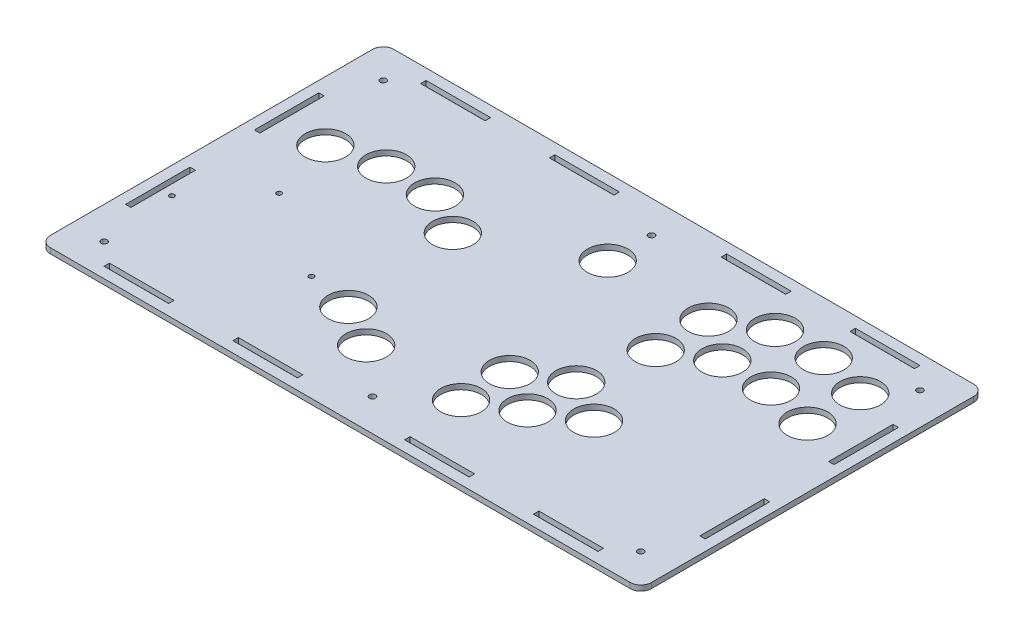
SolidWorks part; units mm, degrees
ref_plane "Front Plane" through (0, 0, 0) normal (0, 0, 1) x (1, 0, 0)
ref_plane "Top Plane" through (0, 0, 0) normal (0, 1, 0) x (1, 0, 0)
ref_plane "Right Plane" through (0, 0, 0) normal (1, 0, 0) x (0, 0, -1)
ref_axis "Axis1" through (0, 0, -135.9953) along (0, 0, 1)
sketch "Panel Profile" plane through (0, 0, 0) normal (0, 1, 0) x (1, 0, 0)
  line L1 (-177.8, 101.6) -> (177.8, 101.6)
  line L2 (-177.8, 101.6) -> (-177.8, -101.6)
  line L3 (-177.8, -101.6) -> (177.8, -101.6)
  line L4 (177.8, 101.6) -> (177.8, -101.6)
  line L5 (-177.8, 101.6) -> (177.8, -101.6) construction
  line L6 (-177.8, -101.6) -> (177.8, 101.6) construction
  point P0 (0, 0)
  dimension "D1" = 203.2
  dimension "D2" = 355.6
sketch "Right Hand Buttons" plane through (0, 0, 0) normal (0, 1, 0) x (1, 0, 0)
  line L0 (85, 70.6) -> (113.8, 70.6) construction
  line L5 (-55, 0) -> (55, 0) construction
  line L6 (0, -55) -> (0, 55) construction
  line L7 (60, 56.2) -> (60, 25) construction
  line L8 (85, 70.6) -> (85, 39.4) construction
  line L9 (113.8, 70.6) -> (113.8, 39.4) construction
  line L10 (142.6, 63.4) -> (142.6, 32.2) construction
  circle A0 centre (60, 56.2) radius 12
  circle A1 centre (85, 70.6) radius 12
  circle A2 centre (113.8, 70.6) radius 12
  circle A7 centre (142.6, 63.4) radius 12
  circle A8 centre (60, 25) radius 12
  circle A9 centre (85, 39.4) radius 12
  circle A10 centre (113.8, 39.4) radius 12
  circle A11 centre (142.6, 32.2) radius 12
  point P0 (0, 0)
  dimension "D2" = 24
  dimension "D1" = 25
  dimension "D3" = 28.8
  dimension "D4" = 14.4
  dimension "D5" = 25
  dimension "D6" = 28.8
  dimension "D7" = 7.2
  dimension "D8" = 31.2
  dimension "D9" = 60
extrude "Panel-Profile" add sketch "Panel Profile" against normal blind 3.175
extrude "Right Buttons" cut sketch "Right Hand Buttons" against normal blind 3.175 and the other way through all
sketch "Sketch4" plane through (0, 0, 0) normal (0, 1, 0) x (1, 0, 0)
  line L0 (28.0585, -29.4) -> (28.0585, -58.2) construction
  line L1 (53, -15) -> (53, -43.8) construction
  line L2 (28.0585, -29.4) -> (53, -15) construction
  line L3 (28.0585, -29.4) -> (53, -43.8) construction
  line L4 (53, -15) -> (77.9415, -29.4) construction
  line L5 (53, -43.8) -> (77.9415, -29.4) construction
  line L6 (28.0585, -58.2) -> (53, -43.8) construction
  circle A0 centre (53, -43.8) radius 12
  circle A1 centre (53, -15) radius 12
  circle A2 centre (77.9415, -29.4) radius 12
  circle A3 centre (28.0585, -29.4) radius 12
  circle A4 centre (28.0585, -58.2) radius 12
  circle A5 centre (60, 25) radius 12 construction
  dimension "D1" = 24
  dimension "D3" = 40
  dimension "D4" = 7
  dimension "D2" = 28.8
extrude "C-Stick" cut sketch "Sketch4" against normal blind 3.175
sketch "Start Button" plane through (0, 0, 0) normal (0, 1, 0) x (1, 0, 0)
  line L0 (0, -55) -> (0, 55) construction
  line L1 (177.8, 101.6) -> (-177.8, 101.6) construction
  circle A0 centre (0, 56.6) radius 12
  dimension "D1" = 24
  dimension "D2" = 45
extrude "Start" cut sketch "Start Button" against normal blind 3.175 contours A0
sketch "Sketch7" plane through (0, 0, 0) normal (0, 1, 0) x (1, 0, 0)
  line L0 (0, -55) -> (0, 55) construction
  circle A0 centre (142.6, 32.2) radius 12 construction
  circle A1 centre (113.8, 39.4) radius 12 construction
  circle A2 centre (85, 39.4) radius 12 construction
  circle A3 centre (60, 25) radius 12 construction
  circle A4 centre (142.6, 32.2) radius 12 construction
  circle A5 centre (113.8, 39.4) radius 12 construction
  circle A6 centre (85, 39.4) radius 12 construction
  circle A7 centre (60, 25) radius 12 construction
  circle A8 centre (-142.6, 32.2) radius 12
  circle A9 centre (-113.8, 39.4) radius 12
  circle A10 centre (-85, 39.4) radius 12
  circle A11 centre (-60, 25) radius 12
  circle A12 centre (28.0585, -58.2) radius 12 construction
  circle A13 centre (53, -43.8) radius 12 construction
  circle A14 centre (28.0585, -58.2) radius 12 construction
  circle A15 centre (53, -43.8) radius 12 construction
  circle A16 centre (-53, -43.8) radius 12
  circle A17 centre (-28.0585, -58.2) radius 12
extrude "L-Stick" cut sketch "Sketch7" against normal blind 3.175
sketch "Sketch8" plane through (0, 0, 0) normal (0, 1, 0) x (1, 0, 0)
  line L0 (0, 135.9953) -> (0, -135.9953) construction
  line L1 (177.8, 101.6) -> (-177.8, 101.6) construction
  line L2 (-177.8, 101.6) -> (-177.8, -101.6) construction
  line L3 (-177.8, -101.6) -> (177.8, -101.6) construction
  line L4 (177.8, -101.6) -> (177.8, 101.6) construction
  circle A0 centre (-158.75, 82.55) radius 1.8288
  circle A1 centre (0, 82.55) radius 1.8288
  circle A2 centre (158.75, 82.55) radius 1.8288
  circle A3 centre (-158.75, -82.55) radius 1.8288
  circle A4 centre (0, -82.55) radius 1.8288
  circle A5 centre (158.75, -82.55) radius 1.8288
  dimension "D1" = 3.6576
  dimension "D2" = 19.05
  dimension "D3" = 19.05
  dimension "D4" = 19.05
  dimension "D5" = 19.05
extrude "Cut-Extrude1" cut sketch "Sketch8" against normal blind 10
fillet "Fillet1" radius 6.35 4 edges at (177.8, -1.5875, -101.6) (177.8, -1.5875, 101.6) (-177.8, -1.5875, 101.6) (-177.8, -1.5875, -101.6)
sketch "Sketch9" plane through (0, 0, 0) normal (0, 1, 0) x (1, 0, 0)
  line L1 (-146.09, 95.25) -> (-107.91, 95.25)
  line L2 (-146.09, 95.25) -> (-146.09, 92)
  line L3 (-146.09, 92) -> (-107.91, 92)
  line L4 (-107.91, 95.25) -> (-107.91, 92)
  line L5 (-69.89, 95.25) -> (-31.71, 95.25)
  line L6 (-69.89, 95.25) -> (-69.89, 92)
  line L7 (-69.89, 92) -> (-31.71, 92)
  line L8 (-31.71, 95.25) -> (-31.71, 92)
  line L9 (171.45, 101.6) -> (-171.45, 101.6) construction
  line L10 (-127, 95.25) -> (-127, 92) construction
  line L11 (-50.8, 95.25) -> (-50.8, 92) construction
  line L12 (0, -1.7463) -> (0, 1.7463) construction
  dimension "D1" = 3.25
  dimension "D2" = 38.18
  dimension "D3" = 76.2
  dimension "D4" = 50.8
  dimension "D5" = 6.35
extrude "Cut-Extrude2" cut sketch "Sketch9" against normal through all both and the other way through all
mirror "Mirror1" about plane through (0, 0, 0) normal (1, 0, 0) of "Cut-Extrude2"
mirror "Mirror2" about plane through (0, 0, 0) normal (0, 0, 1) of "Mirror1", "Cut-Extrude2"
sketch "Sketch10" plane through (0, 0, 0) normal (0, 1, 0) x (1, 0, 0)
  line L0 (-171.45, 38.1) -> (-168.2496, 38.1) construction
  line L1 (-171.45, 57.1627) -> (-168.2496, 57.1627)
  line L2 (-171.45, 57.1627) -> (-171.45, 19.0373)
  line L3 (-171.45, 19.0373) -> (-168.2496, 19.0373)
  line L4 (-168.2496, 57.1627) -> (-168.2496, 19.0373)
  line L5 (-1.7463, 0) -> (1.7463, 0) construction
  line L6 (-177.8, 95.25) -> (-177.8, -95.25) construction
  dimension "D1" = 3.2004
  dimension "D2" = 38.1254
  dimension "D3" = 38.1
  dimension "D4" = 6.35
extrude "Cut-Extrude3" cut sketch "Sketch10" against normal through all both and the other way through all
mirror "Mirror3" about plane through (0, 0, 0) normal (0, 0, 1) of "Cut-Extrude3"
mirror "Mirror4" about plane through (0, 0, 0) normal (1, 0, 0) of "Cut-Extrude3", "Mirror3"
sketch "Sketch12" plane through (0, -3.175, 0) normal (0, -1, 0) x (1, 0, 0)
  line L0 (-168.2496, 19.0373) -> (-168.2496, 57.1627) construction
  line L1 (-65.6496, 41.6) -> (-167.2496, 41.6) construction
  line L2 (-65.6496, 41.6) -> (-65.6496, -11.74) construction
  line L3 (-65.6496, -11.74) -> (-167.2496, -11.74) construction
  line L4 (-167.2496, 41.6) -> (-167.2496, -11.74) construction
  line L5 (-171.45, 101.6) -> (171.45, 101.6) construction
  circle A0 centre (-79.6196, 39.06) radius 1.4732
  circle A1 centre (-131.6896, 6.04) radius 1.4732
  circle A2 centre (-162.1696, 39.06) radius 1.4732
  dimension "D3" = 2.9464
  dimension "D8" = 96.52
  dimension "D1" = 101.6
  dimension "D2" = 53.34
  dimension "D4" = 13.97
  dimension "D5" = 2.54
  dimension "D6" = 66.04
  dimension "D7" = 35.56
  dimension "D9" = 2.54
  dimension "D10" = 1
  dimension "D11" = 60
extrude "Cut-Extrude4" cut sketch "Sketch12" against normal through all both and the other way through all
equation "\"button_diam\"= 24mm'Button Diameter"
equation "\"x_spacing\"= 0'Horizonal Button Spacing"
equation "\"y_spacing\"= 0'Vertical Button Spacing"
equation "\"slant\"= 0'Difference between Top and Buttom Row"
equation "\"teeth\"= 1.5in'Teeth Size for Box"
equation "\"teeth_tol\"= 0.001in'Tolerance of Meshing Teeth"
equation "\"t\"= 0.125in'Sheet Thickness"
equation "\"D1@Sketch10\"=\"t\"+\"teeth_tol\""
equation "\"D2@Sketch10\"=\"teeth\"+\"teeth_tol\""
equation "\"hole_offset\"= 0.75in'Distance from Edge to Mounting Holes"
equation "\"D2@Sketch8\"=\"hole_offset\""
equation "\"D3@Sketch8\"=\"hole_offset\""
equation "\"D4@Sketch8\"=\"hole_offset\""
equation "\"D5@Sketch8\"=\"hole_offset\""
